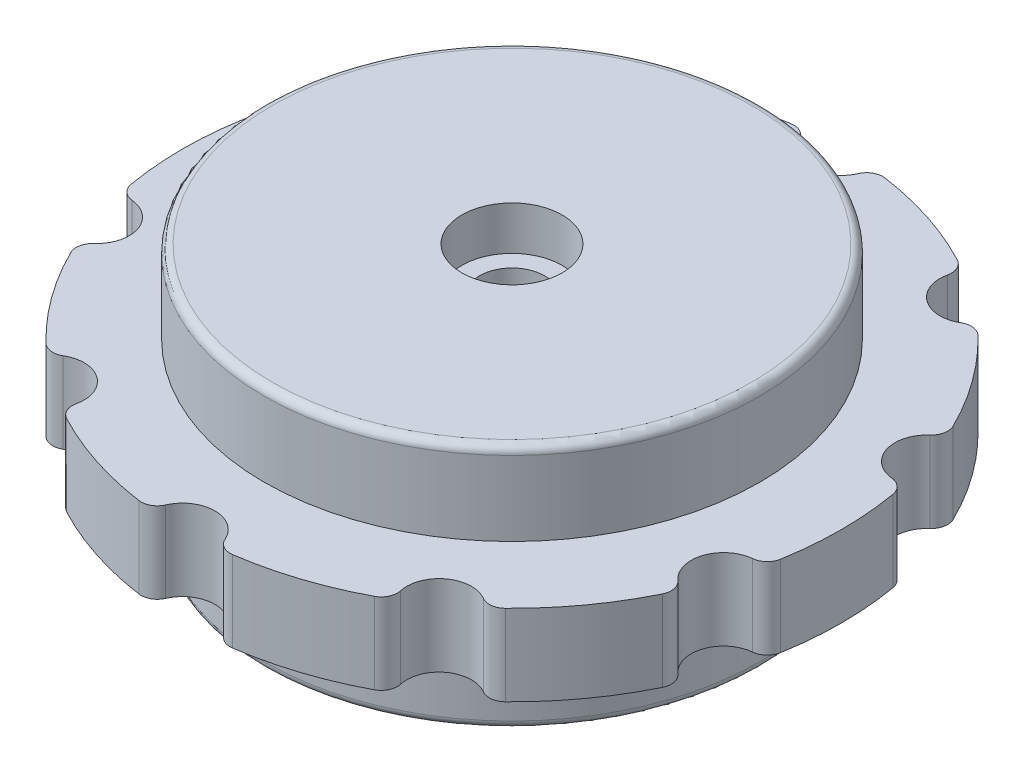
SolidWorks part; units mm, degrees
ref_plane "前视基准面" through (0, 0, 0) normal (0, 0, 1) x (1, 0, 0)
ref_plane "上视基准面" through (0, 0, 0) normal (0, 1, 0) x (1, 0, 0)
ref_plane "右视基准面" through (0, 0, 0) normal (1, 0, 0) x (0, 0, -1)
other "Configuration Table"
sketch "草图1" plane through (0, 0, 0) normal (0, 1, 0) x (1, 0, 0)
  circle A0 centre (0, 0) radius 15.3
  circle A1 centre (0, 0) radius 20.35
  circle A2 centre (0, 0) radius 13.7
  circle A3 centre (0, 20.35) radius 2
  dimension "D1" = 30.6
  dimension "D2" = 40.7
  dimension "D3" = 1.6
  dimension "D4" = 4
extrude "凸台-拉伸1" add sketch "草图1" along normal mid plane 15.2 contours A0 | A2
extrude "凸台-拉伸2" add sketch "草图1<3>" along normal mid plane 5 contours A1
sketch "草图1<3>" plane through (0, 0, 0) normal (0, 1, 0) x (1, 0, 0) same geometry as "草图1"
extrude "切除-拉伸1" cut sketch "草图1<4>" against normal through all both and the other way through all contours A3
sketch "草图1<4>" plane through (0, 0, 0) normal (0, 1, 0) x (1, 0, 0) same geometry as "草图1"
fillet "圆角1" radius 1 2 edges at (1.9976, 0, -20.2517) (-1.9976, 0, -20.2517)
pattern_circular "阵列(圆周)1" count 10 over 360 about axis through (0, 2.5, 0) along (0, -1, 0) of "切除-拉伸1", "圆角1"
fillet "圆角2" radius 0.5 2 edges at (0, -7.6, 15.3) (0, 7.6, 15.3)
extrude "凸台-拉伸3" add sketch "草图1<5>" along normal mid plane 7.8 contours A2
sketch "草图1<5>" plane through (0, 0, 0) normal (0, 1, 0) x (1, 0, 0) same geometry as "草图1"
extrude "凸台-拉伸5" add sketch "草图1<6>" along normal up to surface (7.6 mm away) from surface contours A2 up to face at (0, 7.6, 14.8) starting at face at (0, -7.6, 14.8)
sketch "草图1<6>" plane through (0, 0, 0) normal (0, 1, 0) x (1, 0, 0) same geometry as "草图1"
sketch "草图2" plane through (0, 2.5, 0) normal (0, 1, 0) x (1, 0, 0)
  line L0 (0, 20.35) -> (11.9614, 16.4635)
  line L1 (-11.9614, 16.4635) -> (0, 20.35)
  arc A0 (-1.834, 19.5523) -> (1.834, 19.5523) centre (0, 20.35) ccw construction
  arc A1 (10.0088, 16.8962) -> (12.9763, 14.7401) centre (11.9614, 16.4635) ccw construction
  arc A2 (-12.9763, 14.7401) -> (-10.0088, 16.8962) centre (-11.9614, 16.4635) ccw construction
  dimension "D1" = 12.577
  dimension "D2" = 12.577
sketch "草图4" plane through (0, -7.6, 0) normal (0, -1, 0) x (1, 0, 0)
  circle A0 centre (0, 0) radius 2
  circle A1 centre (0, 0) radius 3.1
  dimension "D1" = 4
  dimension "D2" = 6.2
extrude "切除-拉伸3" cut sketch "草图4" against normal through all contours A0
extrude "切除-拉伸4" cut sketch "草图4<3>" against normal blind 2.7 contours A1
sketch "草图4<3>" plane through (0, -7.6, 0) normal (0, -1, 0) x (1, 0, 0) same geometry as "草图4"
extrude "切除-拉伸5" cut sketch "草图4<4>" along normal blind 2.7 from surface contours A1 starting at face at (0, 7.6, -2)
sketch "草图4<4>" plane through (0, -7.6, 0) normal (0, -1, 0) x (1, 0, 0) same geometry as "草图4"
sketch "草图5" plane through (0, -7.6, 0) normal (0, -1, 0) x (1, 0, 0)
  circle A0 centre (0, 0) radius 13
  dimension "D1" = 26
extrude "切除-拉伸6" cut sketch "草图5" against normal blind 4.5
sketch "草图6" plane through (0, -3.1, 0) normal (0, -1, 0) x (1, 0, 0)
  circle A0 centre (0, 0) radius 2.75
  dimension "D1" = 5.5
extrude "切除-拉伸7" cut sketch "草图6" against normal blind 2
sketch "草图7" plane through (0, -3.1, 0) normal (0, -1, 0) x (1, 0, 0)
  circle A0 centre (-8, 0) radius 0.75
  circle A1 centre (4, 6.9282) radius 0.75
  circle A2 centre (4, -6.9282) radius 0.75
  point P9 (0, 0)
  dimension "D1" = 1.5
  dimension "D2" = 8
  dimension "D3" = 3
extrude "切除-拉伸8" cut sketch "草图7" against normal blind 5 contours A0 | A1 | A2
